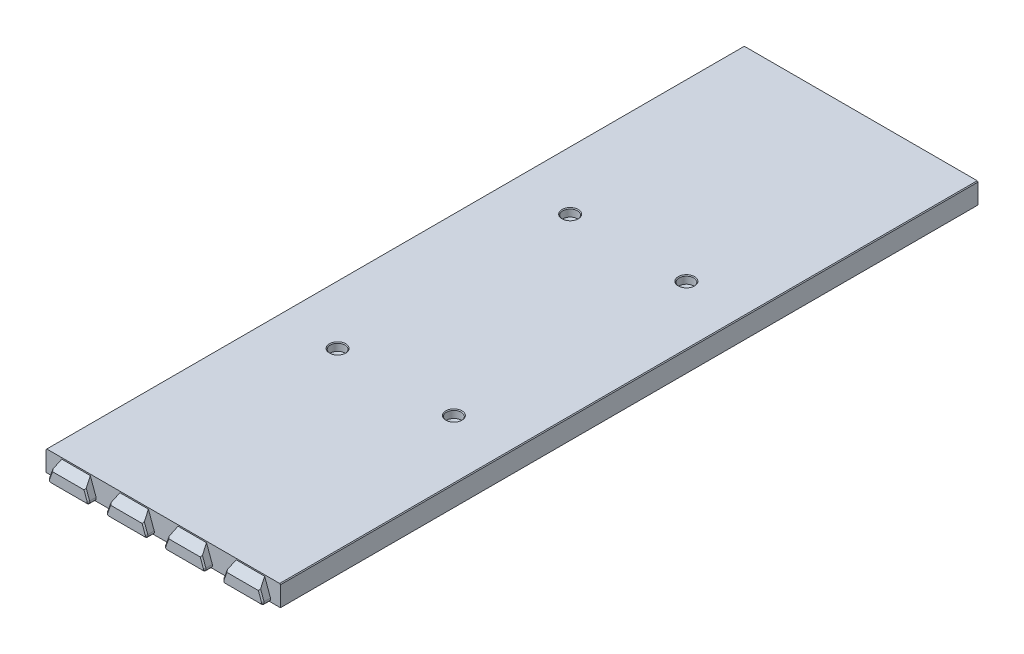
SolidWorks part; units mm, degrees
ref_plane "Front Plane" through (0, 0, 0) normal (0, 0, 1) x (1, 0, 0)
ref_plane "Top Plane" through (0, 0, 0) normal (0, 1, 0) x (1, 0, 0)
ref_plane "Right Plane" through (0, 0, 0) normal (1, 0, 0) x (0, 0, -1)
sketch "Sketch1" plane through (0, 0, 0) normal (0, 0, 1) x (1, 0, 0)
  line L0 (0, 0) -> (0, 8) construction
  line L1 (-45.375, 0) -> (0, 0) construction
  line L2 (-45.375, 0) -> (-45.375, 8)
  line L3 (-45.375, 8) -> (45.375, 8)
  line L5 (-45.375, 0) -> (-43.375, 0)
  line L6 (-43.375, 0) -> (-43.375, 6)
  line L7 (-43.375, 6) -> (43.375, 6)
  line L9 (43.375, 0) -> (43.375, 6)
  line L10 (45.375, 0) -> (43.375, 0)
  line L11 (45.375, 0) -> (45.375, 8)
  point P8 (0, 6)
  dimension "D2" = 6
  dimension "D1" = 45.375
  dimension "D3" = 2
  dimension "D4" = 2
extrude "Boss-Extrude1" add sketch "Sketch1" against normal blind 135
sketch "Sketch7" plane through (0, 0, 0) normal (0, 0, 1) x (1, 0, 0)
  line L2 (-43.375, 0) -> (43.375, 0)
  line L13 (-43.375, 0) -> (-43.375, 6)
  line L15 (-43.375, 6) -> (43.375, 6)
  line L16 (43.375, 0) -> (43.375, 6)
  line M3 (-43.375, 0) -> (-43.375, 6)
  line M4 (-43.375, 6) -> (43.375, 6)
  line M5 (43.375, 6) -> (43.375, 0)
extrude "Boss-Extrude7" add sketch "Sketch7" against normal blind 1 contours M4 M3 | M5 region at (0, 3, 0)
sketch "Sketch2" plane through (0, 0, 0) normal (0, 0, 1) x (1, 0, 0)
  line L14 (28.4118, 8) -> (25.5, 0)
  line L15 (45.375, 8) -> (-45.375, 8) construction
  line L16 (-45.375, 0) -> (45.375, 0) construction
  line L17 (25.5, 0) -> (42, 0)
  line L18 (28.4118, 8) -> (39.0882, 8)
  line L19 (-45.375, 0) -> (45.375, 0) construction
  line L21 (39.0882, 8) -> (42, 0)
  line L24 (22.5, 0) -> (22.5, 8) construction
  line L27 (5.9118, 8) -> (3, 0)
  line L28 (5.9118, 8) -> (16.5882, 8)
  line L29 (3, 0) -> (19.5, 0)
  line L30 (16.5882, 8) -> (19.5, 0)
  line L31 (-16.5882, 8) -> (-19.5, 0)
  line L32 (-16.5882, 8) -> (-5.9118, 8)
  line L33 (-19.5, 0) -> (-3, 0)
  line L34 (-5.9118, 8) -> (-3, 0)
  line L35 (-39.0882, 8) -> (-42, 0)
  line L36 (-39.0882, 8) -> (-28.4118, 8)
  line L37 (-42, 0) -> (-25.5, 0)
  line L38 (-28.4118, 8) -> (-25.5, 0)
  line L39 (28.4118, 8) -> (5.9118, 8) construction
  line L40 (45, 8) -> (45, 0) construction
  line L41 (45.375, 0) -> (45.375, 8) construction
  line L42 (-45, 8) -> (-45, 0) construction
  line L43 (-45.375, 8) -> (-45.375, 0) construction
  point P22 (33.75, 8)
  point P23 (11.25, 8)
  dimension "D1" = 70
  dimension "D2" = 0.375
  dimension "D3" = 3
  dimension "D4" = 3
  dimension "D5" = 70
  dimension "D7" = 22.5
  dimension "D8" = 22.5
  dimension "D9" = 0.375
  dimension "D10" = 3
  dimension "D11" = 8
  dimension "D6" = 4
extrude "Boss-Extrude4" add sketch "Sketch2" along normal blind 3
sketch "Sketch8" plane through (0, 0, 0) normal (0, -1, 0) x (1, 0, 0)
  line L0 (-45.375, -22.5) -> (45.375, -22.5) construction
  line L1 (-43.85, -20.2583) -> (-40.15, -21.605)
  line L2 (45.375, -135) -> (45.375, 0) construction
  line L3 (-45.375, 0) -> (-42, 0) construction
  line L4 (-44, -24.9559) -> (-44, -20.0441) construction
  line L5 (-44, -20.0441) -> (-40, -21.5) construction
  line L6 (-40, -21.5) -> (-40, -23.5) construction
  line L7 (-44, -135) -> (-44, -132.5441) construction
  line L8 (-44, -132.5441) -> (-40, -134) construction
  line L9 (-40, -134) -> (-40, -135) construction
  line L10 (-43.375, -135) -> (43.375, -135) construction
  line L11 (-40, -135) -> (-44, -135) construction
  line L12 (-44, -24.9559) -> (-40, -23.5) construction
  line L13 (0, -135) -> (0, 0) construction
  line L22 (-40.15, -21.605) -> (-40.15, -23.395)
  line L23 (-45.375, -135) -> (-45.375, 0) construction
  line L28 (-45.375, -135) -> (-43.375, -135) construction
  line L33 (-43.85, -24.7417) -> (-40.15, -23.395)
  line L34 (-43.85, -24.7417) -> (-43.85, -20.2583)
  line L35 (-43.85, -132.7583) -> (-40.15, -134.105)
  line L36 (-40.15, -134.105) -> (-40.15, -134.85)
  line L37 (-40.15, -134.85) -> (-43.85, -134.85) construction
  line L38 (-43.85, -134.85) -> (-43.85, -132.7583)
  line L39 (-43.85, -134.85) -> (-43.85, -135)
  line L40 (-43.85, -135) -> (-40.15, -135)
  line L41 (-40.15, -135) -> (-40.15, -134.85)
  line L42 (43.85, -135) -> (40.15, -135)
  line L43 (43.85, -134.85) -> (43.85, -135)
  line L44 (43.85, -134.85) -> (43.85, -132.7583)
  line L45 (43.85, -132.7583) -> (40.15, -134.105)
  line L46 (40.15, -134.105) -> (40.15, -134.85)
  line L47 (40.15, -135) -> (40.15, -134.85)
  line L48 (43.85, -24.7417) -> (43.85, -20.2583)
  line L49 (43.85, -24.7417) -> (40.15, -23.395)
  line L50 (40.15, -21.605) -> (40.15, -23.395)
  line L51 (43.85, -20.2583) -> (40.15, -21.605)
  point P19 (-40, -22.5)
  dimension "D1" = 22.5
  dimension "D2" = 1.375
  dimension "D3" = 70
  dimension "D4" = 4
  dimension "D5" = 0.15
  dimension "D6" = 4
  dimension "D7" = 70
  dimension "D8" = 1
  dimension "D9" = 1
  dimension "D10" = 0.15
extrude "Boss-Extrude8" add sketch "Sketch8" against normal up to next and the other way blind 2
chamfer "Chamfer4" distance 0.5 angle 45 14 edges at (40.15, -2, -22.5) (42, -2, -20.9317) (43.85, -2, -22.5) (42, -2, -24.0683) (-42, -2, -20.9317) (-40.15, -2, -22.5) (-42, -2, -24.0683) (-43.85, -2, -22.5) (-40.15, -2, -134.5525) (-42, -2, -133.4317) (-43.85, -2, -133.8792) (40.15, -2, -134.5525) (42, -2, -133.4317) (43.85, -2, -133.8792)
fillet "Fillet4" radius 1 8 edges at (42, 0, 1.5) (25.5, 0, 1.5) (19.5, 0, 1.5) (3, 0, 1.5) (-3, 0, 1.5) (-19.5, 0, 1.5) (-25.5, 0, 1.5) (-42, 0, 1.5)
chamfer "Chamfer6" distance 0.5 angle 45 20 edges at (27.2001, 4.671, 3) (40.2999, 4.671, 3) (33.75, 0, 3) (-40.2999, 4.671, 3) (-33.75, 0, 3) (-27.2001, 4.671, 3) (-17.7999, 4.671, 3) (-11.25, 0, 3) (-4.7001, 4.671, 3) (4.7001, 4.671, 3) (17.7999, 4.671, 3) (11.25, 0, 3) (-41.391, 0.4264, 3) (-26.109, 0.4264, 3) (-18.891, 0.4264, 3) (-3.609, 0.4264, 3) (3.609, 0.4264, 3) (18.891, 0.4264, 3) (26.109, 0.4264, 3) (41.391, 0.4264, 3)
fillet "Fillet2" radius 2 23 edges at (0, 6, -1) (-43.375, 3, -1) (43.375, 6, -10.7156) (43.375, 3, -1) (-43.375, 6, -10.7156) (43.375, 3, -20.4312) (41.7625, 6, -21.0181) (40.15, 6, -22.5) (41.7625, 6, -23.9819) (43.375, 3, -24.5688) (43.375, 6, -78.75) (43.375, 3, -132.9312) (41.7625, 6, -133.5181) (40.15, 6, -134.5525) (-40.15, 6, -134.5525) (-41.7625, 6, -133.5181) (-43.375, 3, -132.9312) (-43.375, 6, -78.75) (-43.375, 3, -24.5688) (-41.7625, 6, -23.9819) (-40.15, 6, -22.5) (-43.375, 3, -20.4312) (-41.7625, 6, -21.0181)
mirror "Mirror2" about plane through (0, 0, -135) normal (0, 0, 1) of "Fillet4", "Boss-Extrude1", "Boss-Extrude7", "Boss-Extrude4", "Boss-Extrude8", "Chamfer4", "Fillet2", "Chamfer6"
sketch "Sketch9" plane through (0, 0, 0) normal (0, 1, 0) x (1, 0, 0)
  line L16 (0, 135) -> (0, 0) construction
  line L17 (-45.375, 135) -> (45.375, 135) construction
  line L20 (45.375, 270) -> (45.375, 0) construction
  line L21 (-45.375, 270) -> (-45.375, 0) construction
  circle A0 centre (-22.5, 90) radius 5
  circle A4 centre (22.5, 90) radius 5
  circle A5 centre (22.5, 180) radius 5
  circle A6 centre (-22.5, 180) radius 5
  point P23 (0, 135)
  point P24 (0, 135)
  dimension "D3" = 10
  dimension "D1" = 22.5
  dimension "D2" = 45
extrude "Boss-Extrude9" add sketch "Sketch9" along normal up to next
fillet "Fillet3" radius 3 4 edges at (-22.5, 6, -95) (22.5, 6, -185) (-22.5, 6, -185) (22.5, 6, -95)
sketch "Sketch10" plane through (0, 0, 0) normal (0, 1, 0) x (1, 0, 0)
  circle A0 centre (-22.5, 180) radius 1.85
  circle A1 centre (-22.5, 90) radius 1.85
  circle A2 centre (22.5, 90) radius 1.85
  circle A3 centre (22.5, 180) radius 1.85
  dimension "D1" = 3.7
extrude "Cut-Extrude2" cut sketch "Sketch10" along normal through all
sketch "Sketch11" plane through (0, 8, 0) normal (0, 1, 0) x (1, 0, 0)
  circle A0 centre (-22.5, 180) radius 2.85
  circle A1 centre (22.5, 180) radius 2.85
  circle A2 centre (22.5, 90) radius 2.85
  circle A3 centre (-22.5, 90) radius 2.85
  dimension "D1" = 5.7
extrude "Cut-Extrude3" cut sketch "Sketch11" against normal blind 3
chamfer "Chamfer7" distance 1 angle 45 4 edges at (22.5, 5, -178.15) (-22.5, 5, -178.15) (22.5, 5, -88.15) (-22.5, 5, -88.15)
sketch "Sketch12" plane through (0, 0, 0) normal (1, 0, 0) x (0, 0, -1)
  line L0 (0, 7.5) -> (-3, 4.5)
  line L1 (-3, 1.171) -> (-3, 8) construction
  line L2 (-3, 4.5) -> (-3, 7.5)
  line L4 (135, 8) -> (135, 0) construction
  line L5 (270, 8) -> (0, 8) construction
  line L6 (270, 0) -> (0, 0) construction
  line L10 (0, 0) -> (0, 8) construction
  line L11 (-3, 7.5) -> (0, 7.5) construction
  line L12 (0, 7.5) -> (0, 8)
  line L13 (0, 8) -> (-3, 8)
  line L14 (-3, 8) -> (-3, 7.5)
  line L15 (273, 7.5) -> (270, 7.5) construction
  line L16 (273, 8) -> (273, 7.5)
  line L17 (270, 8) -> (273, 8)
  line L18 (270, 7.5) -> (270, 8)
  line L19 (273, 4.5) -> (273, 7.5)
  line L20 (270, 7.5) -> (273, 4.5)
  dimension "D1" = 0.5
  dimension "D2" = 3
  dimension "D3" = 45
extrude "Cut-Extrude4" cut sketch "Sketch12" against normal through all both and the other way through all
chamfer "Chamfer8" distance 0.3 angle 45 6 edges at (22.5, 8, -87.15) (22.5, 8, -177.15) (-22.5, 8, -87.15) (-22.5, 8, -177.15) (-45.375, 8, -135) (45.375, 8, -135)
